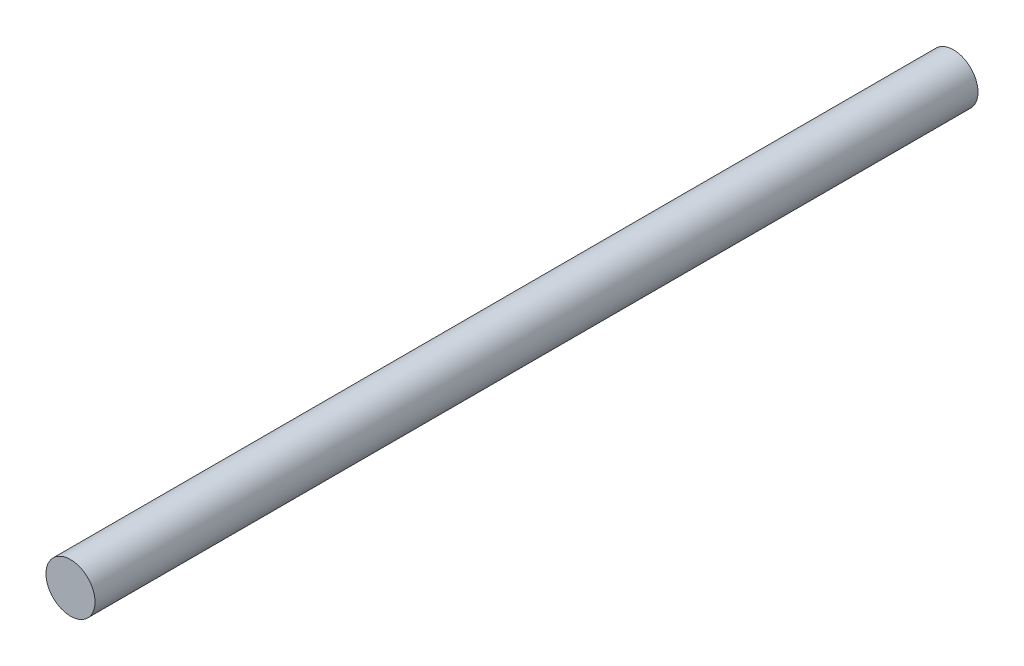
SolidWorks part; units mm, degrees
ref_plane "Front Plane" through (0, 0, 0) normal (0, 0, 1) x (1, 0, 0)
ref_plane "Top Plane" through (0, 0, 0) normal (0, 1, 0) x (1, 0, 0)
ref_plane "Right Plane" through (0, 0, 0) normal (1, 0, 0) x (0, 0, -1)
sketch "Sketch1" plane through (0, 0, 0) normal (0, 0, 1) x (1, 0, 0)
  line L1 (-3.175, 0) -> (3.175, 0) construction
  dimension "OD" = 6.35
sketch "Sketch2" plane through (0, 0, 0) normal (1, 0, 0) x (0, 0, -1)
  line L0 (57.15, 0) -> (-57.15, 0)
  point P0 (-42.8625, 0)
  point P3 (42.8625, 0)
  point P4 (0, 0)
  dimension "Length" = 114.3
  dimension "D1" = 14.2875
  dimension "D2" = 14.2875
sketch "Sketch3" plane through (0, 0, 0) normal (0, 0, 1) x (1, 0, 0)
  circle A0 centre (0, 0) radius 3.175
extrude "Boss-Extrude1" add sketch "Sketch3" along normal up to vertex (57.15 mm away) and the other way up to vertex (57.15 mm away) up to point (0, 0, 57.15) other way up to point (0, 0, -57.15)
equation "\"D1@Sketch2\"=\"Length@Sketch2\"/8"
equation "\"D2@Sketch2\"=\"D1@Sketch2\""
